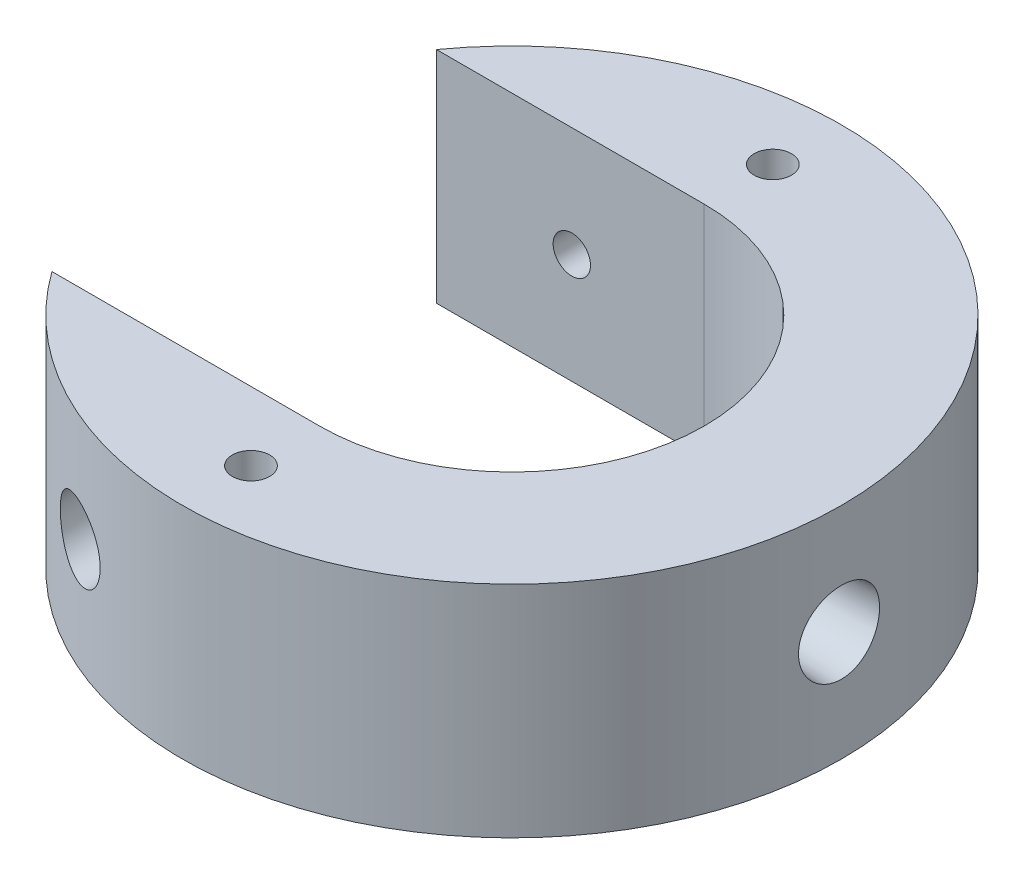
SolidWorks part; units mm, degrees
ref_plane "Front Plane" through (0, 0, 0) normal (0, 0, 1) x (1, 0, 0)
ref_plane "Top Plane" through (0, 0, 0) normal (0, 1, 0) x (1, 0, 0)
ref_plane "Right Plane" through (0, 0, 0) normal (1, 0, 0) x (0, 0, -1)
sketch "Sketch2" plane through (0, 0, 0) normal (0, 1, 0) x (1, 0, 0)
  circle A0 centre (0, 0) radius 30
  dimension "D1" = 60
extrude "Boss-Extrude1" add sketch "Sketch2" along normal blind 20
sketch "Sketch3" plane through (0, 20, 0) normal (0, 1, 0) x (1, 0, 0)
  line L0 (-24.367, 17.5) -> (-19.1, 17.5)
  line L1 (-19.1, 17.5) -> (-19.1, 21.5)
  line L2 (-19.1, 21.5) -> (0, 21.5)
  line L3 (0, 21.5) -> (0, 17.5)
  line L4 (0, -21.5) -> (0, -17.5)
  line L5 (0, -21.5) -> (-19.1, -21.5)
  line L6 (-19.1, -21.5) -> (-19.1, -17.5)
  line L7 (-19.1, -17.5) -> (-24.367, -17.5)
  line L9 (-13.1, 13.5) -> (-23.1, 13.5)
  line L10 (-23.1, 13.5) -> (-23.1, 8.5)
  line L11 (-23.1, 8.5) -> (-11.1, 8.5)
  line L12 (-11.1, 8.5) -> (-11.1, 2.5)
  line L13 (-11.1, 2.5) -> (-23.1, 2.5)
  line L14 (-23.1, 2.5) -> (-23.1, -2.5)
  line L15 (-23.1, -2.5) -> (-11.1, -2.5)
  line L16 (-11.1, -2.5) -> (-11.1, -8.5)
  line L17 (-11.1, -8.5) -> (-23.1, -8.5)
  line L18 (-23.1, -8.5) -> (-23.1, -13.5)
  line L22 (-23.1, -13.5) -> (-11.1, -13.5)
  line L23 (-2, 6.8125) -> (-2, 9.0619)
  line L25 (-2, -6.8125) -> (-2, -9.0619)
  line L28 (-2, -9.0619) -> (-2, -17.5)
  line L29 (-2, 9.0619) -> (-2, 17.5)
  line L30 (0, 17.5) -> (0, -17.5) construction
  line L31 (-2, 17.5) -> (0, 17.5)
  line L32 (-2, -17.5) -> (0, -17.5)
  circle A0 centre (0, 0) radius 30 construction
  arc A1 (0, 17.5) -> (0, -17.5) centre (0, 0) cw
  arc A2 (-24.367, 17.5) -> (-24.367, -17.5) centre (0, 0) ccw
  arc A4 (0, 5.1) -> (0, -5.1) centre (0, 0) ccw construction
  arc A5 (-13.1, 13.5) -> (-2, 9.0619) centre (-13.1, -2.6) cw
  arc A6 (-2, 6.8125) -> (-2, -6.8125) centre (0, 0) ccw
  arc A7 (-11.1, -13.5) -> (-2, -9.0619) centre (-11.1, -1.9515) ccw
  point P35 (-23.1, 0)
  point P36 (-7.1, 0)
  dimension "D9" = 13.1
  dimension "D7" = 2
  dimension "D12" = 5.1
  dimension "D10" = 16.1
  dimension "D2" = 4
  dimension "D3" = 35
  dimension "D4" = 4
  dimension "D5" = 5
  dimension "D6" = 5
  dimension "D8" = 19.1
  dimension "D11" = 12
  dimension "D13" = 2
  dimension "D14" = 4
extrude "Cut-Extrude2" cut sketch "Sketch3" against normal through all contours A6 A1 region at (5.4667, 20, 0)
hole_wizard "M3 Clearance Hole1" positions "Sketch4" profile "Sketch5" hole size "M3" standard "ANSI Metric" end condition through all
sketch "Sketch4" plane through (0, 0, 0) normal (0, -1, 0) x (-1, 0, 0)
  line L9 (0, 30) -> (0, 17.5) construction
  line L11 (0, -30) -> (0, -17.5) construction
  line L13 (-30, 0) -> (-17.5, 0) construction
  circle A3 centre (0, 0) radius 30 construction
  arc A4 (0, 17.5) -> (0, -17.5) centre (0, 0) ccw construction
  point P0 (0, 23.75)
  point P4 (0, -23.75)
  point P76 (0, 23.75)
  point P78 (0, -23.75)
sketch "Sketch5" plane through (0, 0, -23.75) normal (1, 0, 0) x (0, 0, -1)
  line L0 (0, 0) -> (0, 20)
  line L1 (0, 20) -> (1.7, 20)
  line L2 (1.7, 20) -> (1.7, 0.025)
  line L3 (1.7, 0.025) -> (1.725, 0)
  line L5 (1.725, 0) -> (0, 0)
  line L6 (-1.7, 0.025) -> (-1.725, 0) construction
  line L11 (0, -6.35) -> (0, 107.95) construction
  dimension "Thru Hole Dia." = 3.4
  dimension "Thru Hole Depth" = 20
  dimension "Near C'Sink Dia." = 3.45
  dimension "Near C'Sink Angle" = 90
sketch "Sketch6" plane through (0, 20, 0) normal (0, 1, 0) x (1, 0, 0)
  line L1 (-24.367, 17.5) -> (-2, 17.5)
  line L2 (-2, 17.5) -> (-2, -17.5)
  line L3 (-2, -17.5) -> (-24.367, -17.5)
  line L4 (-2, 6.8125) -> (-2, 17.5) construction
  arc A0 (-24.367, 17.5) -> (-24.367, -17.5) centre (0, 0) ccw
  circle A1 centre (0, 0) radius 30 construction
  point P3 (-2, 0)
extrude "Cut-Extrude3" cut sketch "Sketch6" against normal through all
ref_plane "Plane2" through (0, 0, 30) normal (0, 0, 1) x (1, 0, 0)
hole_wizard "CBORE for M3 SHCS1" positions "Sketch7" profile "Sketch8" counterbore size "M3" standard "ANSI Metric" end condition up to next
sketch "Sketch7" plane through (0, 0, 30) normal (0, 0, 1) x (1, 0, 0)
  line L2 (-24.367, 0) -> (-24.367, 20) construction
  point P2 (-12.047, 10)
  point P12 (-24.367, 10)
  dimension "D1" = 12.32
sketch "Sketch8" plane through (-12.047, 10, 30) normal (1, 0, 0) x (0, -1, 0)
  line L0 (0, 0) -> (0, 12.5)
  line L1 (0, 12.5) -> (1.7, 12.5)
  line L3 (1.7, 12.5) -> (1.7, 7)
  line L4 (3.25, 7) -> (1.7, 7)
  line L5 (3.25, 7) -> (3.25, 0.025)
  line L6 (3.25, 0.025) -> (3.275, 0)
  line L7 (3.275, 0) -> (0, 0)
  line L8 (-3.25, 0.025) -> (-3.275, 0) construction
  line L11 (0, -6.35) -> (0, 107.95) construction
  dimension "Thru Hole Dia." = 3.4
  dimension "Thru Hole Depth" = 12.5
  dimension "C'Bore Dia." = 6.5
  dimension "C'Bore Depth" = 7
  dimension "Near C'Sink Dia." = 6.55
  dimension "Near C'Sink Angle" = 90
mirror "Mirror1" about plane through (0, 0, 0) normal (0, 0, 1) of "CBORE for M3 SHCS1"
ref_plane "Plane3" through (30, 0, 0) normal (-1, 0, 0) x (0, 0, 1)
hole_wizard "Hole1" positions "Sketch11" profile "Sketch12" legacy end condition through all
sketch "Sketch11" plane through (30, 0, 0) normal (-1, 0, 0) x (0, 0, 1)
  line L0 (0, -11) -> (0, 11) construction
  line L1 (17.5, 20) -> (17.5, 0) construction
  line L2 (30, 20) -> (-30, 20) construction
  line L3 (-30, 0) -> (30, 0) construction
  point P0 (0, 10)
  point P14 (17.5, 10)
  point P15 (11.8536, 20)
  point P16 (17.5, 0)
sketch "Sketch12" plane through (30, 10, 0) normal (0, 1, 0) x (0, 0, -1)
  line L0 (0, 0) -> (0, 54.367)
  line L1 (0, 54.367) -> (3.4, 54.367)
  line L2 (3.4, 54.367) -> (3.4, 6)
  line L3 (3.4, 6) -> (3.7, 6)
  line L4 (3.7, 6) -> (3.7, 0)
  line L5 (3.7, 0) -> (0, 0)
  line L6 (0, 110) -> (0, -10) construction
  dimension "Diameter" = 6.8
  dimension "Depth" = 54.367
  dimension "C-Bore Diameter" = 7.4
  dimension "C-Bore Depth" = 6
chamfer "Chamfer1" distance 6 distance2 0.3 1 edges at (24, 10, -3.7) first distance on face at (24, 10, -3.7)
